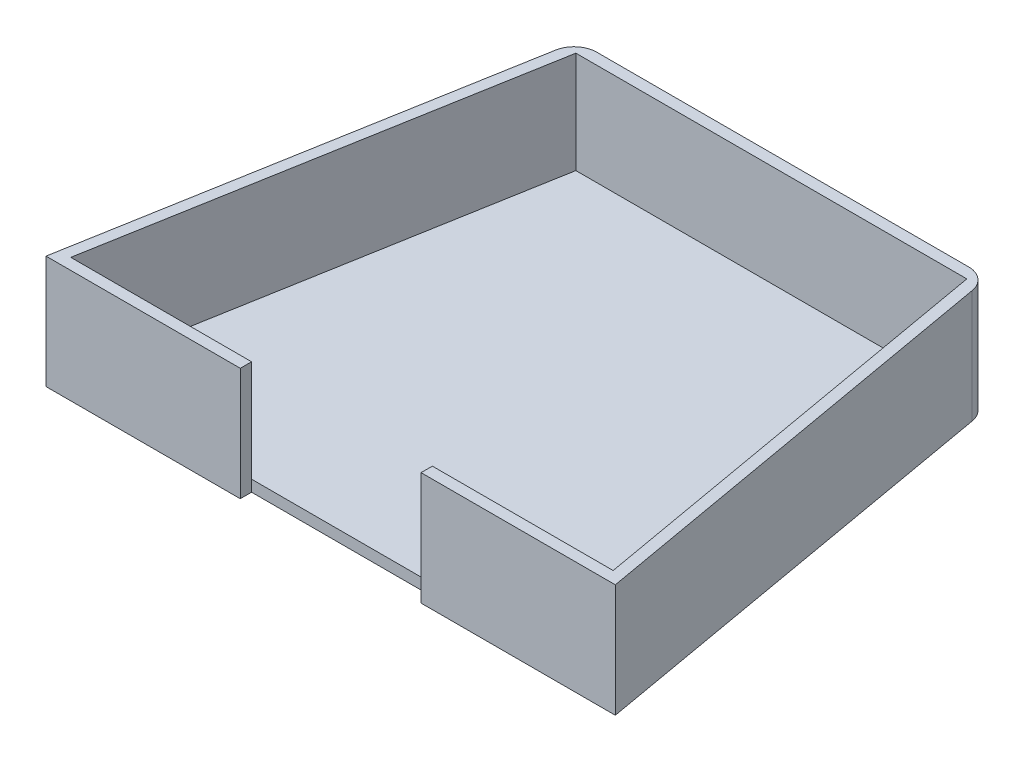
SolidWorks part; units mm, degrees
ref_plane "Front Plane" through (0, 0, 0) normal (0, 0, 1) x (1, 0, 0)
ref_plane "Top Plane" through (0, 0, 0) normal (0, 1, 0) x (1, 0, 0)
ref_plane "Right Plane" through (0, 0, 0) normal (1, 0, 0) x (0, 0, -1)
sketch "Sketch1" plane through (0, 0, 0) normal (0, 1, 0) x (1, 0, 0)
  line L0 (0, 0) -> (33.5021, 190)
  line L3 (240, 0) -> (0, 0)
  line L4 (33.5021, 190) -> (206.4979, 190)
  line L5 (206.4979, 190) -> (240, 0)
  dimension "D1" = 80
  dimension "D2" = 80
  dimension "D3" = 240
  dimension "D4" = 190
extrude "Extrude-Thin1" add sketch "Sketch1" along normal blind 50 thin contours L3 L0 L4 L5 thin type one direction wall 5
extrude "Boss-Extrude1" add sketch "Sketch1<3>" along normal blind 5 separate body
sketch "Sketch1<3>" plane through (0, 0, 0) normal (0, 1, 0) x (1, 0, 0) same geometry as "Sketch1"
fillet "Fillet1" radius 10 2 edges at (210.6934, 25, -195) (29.3066, 25, -195)
sketch "Sketch2" plane through (0, 0, 5) normal (0, 0, 1) x (1, 0, 0)
  line L0 (120, 50) -> (120, 0) construction
  line L1 (245.9588, 50) -> (-5.9588, 50) construction
  line L2 (245.9588, 0) -> (-5.9588, 0) construction
  line L3 (80, 50) -> (80, 0)
  line L4 (160, 50) -> (160, 0)
  line L6 (80, 50) -> (160, 50)
  line L7 (80, 50) -> (80, 0)
  line L8 (80, 0) -> (160, 0)
  line L9 (160, 50) -> (160, 0)
  line M2 (-5.9588, 0) -> (245.9588, 0)
  line M4 (245.9588, 50) -> (-5.9588, 50)
  dimension "D1" = 40
  dimension "D2" = 40
extrude "Cut-Extrude1" cut sketch "Sketch2" against normal blind 5 contours L0 L6 L3 M2 | L0 L8 L4 M4 region at (140, 25, 5) region at (100, 25, 5)
